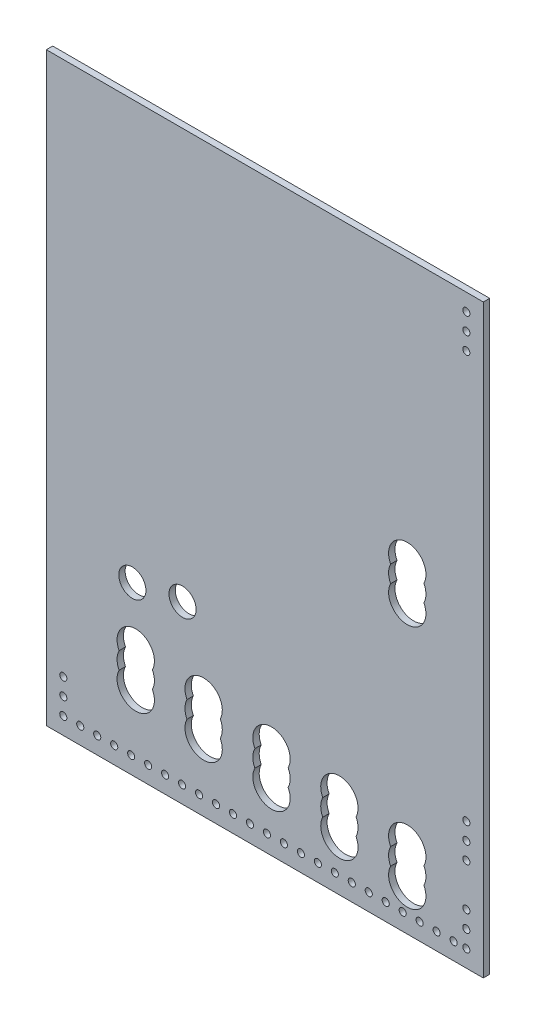
SolidWorks part; units mm, degrees
material "Polypropylene"
ref_plane "Front Plane" through (0, 0, 0) normal (0, 0, 1) x (1, 0, 0)
ref_plane "Top Plane" through (0, 0, 0) normal (0, 1, 0) x (1, 0, 0)
ref_plane "Right Plane" through (0, 0, 0) normal (1, 0, 0) x (0, 0, -1)
sketch "Sketch1" plane through (0, 0, 0) normal (0, 0, 1) x (1, 0, 0)
  line L0 (270.1144, -382.3444) -> (270.1144, -198.1944) construction
  line L1 (0, 0) -> (327.025, 0)
  line L2 (0, 0) -> (0, -438.15)
  line L3 (0, -438.15) -> (327.025, -438.15)
  line L4 (327.025, 0) -> (327.025, -438.15)
  line L5 (270.1144, -198.1944) -> (270.1144, -210.8944) construction
  line L6 (270.1144, -210.8944) -> (270.1144, -223.5944) construction
  arc A2 (257.671, -204.5444) -> (257.671, -217.2444) centre (270.1144, -210.8944) ccw
  arc A3 (257.671, -217.2444) -> (282.5578, -217.2444) centre (270.1144, -223.5944) ccw
  arc A4 (282.5578, -204.5444) -> (257.671, -204.5444) centre (270.1144, -198.1944) ccw
  circle A5 centre (101.9257, -306.8134) radius 10.16
  circle A6 centre (64.3744, -313.2564) radius 10.16
  arc A7 (282.5578, -217.2444) -> (282.5578, -204.5444) centre (270.1144, -210.8944) ccw
  dimension "D4" = 27.94
  dimension "D5" = 20.32
  dimension "D6" = 20.32
  dimension "D1" = 438.15
  dimension "D2" = 327.025
  dimension "D3" = 184.15
extrude "Boss-Extrude1" add sketch "Sketch1" along normal blind 4.7625
sketch "Sketch2" plane through (0, 0, 4.7625) normal (0, 0, 1) x (1, 0, 0)
  line L0 (66.9144, -355.9045) -> (66.9144, -368.6045) construction
  line L1 (66.9144, -368.6045) -> (66.9144, -381.3045) construction
  arc A0 (54.471, -362.2545) -> (54.471, -374.9545) centre (66.9144, -368.6045) ccw
  arc A2 (54.471, -374.9545) -> (79.3578, -374.9545) centre (66.9144, -381.3045) ccw
  arc A3 (79.3578, -374.9545) -> (79.3578, -362.2545) centre (66.9144, -368.6045) ccw
  arc A4 (79.3578, -362.2545) -> (54.471, -362.2545) centre (66.9144, -355.9045) ccw
  dimension "D2" = 27.94
extrude "Cut-Extrude1" cut sketch "Sketch2" against normal up to surface (4.7625 mm away) up to face at (74.5344, -313.2564, 0)
sketch "Sketch3" plane through (0, 0, 4.7625) normal (0, 0, 1) x (1, 0, 0)
  line L0 (66.9144, -355.9045) -> (327.025, -355.9045) construction
  line L1 (327.025, -438.15) -> (327.025, 0) construction
  line L2 (66.9144, -355.9045) -> (117.7144, -355.9045) construction
  line L3 (117.7144, -355.9045) -> (168.5144, -355.9045) construction
  line L4 (168.5144, -355.9045) -> (219.3144, -355.9045) construction
  line L5 (219.3144, -355.9045) -> (270.1144, -355.9045) construction
  line L6 (117.7144, -355.9045) -> (117.7144, -362.2545) construction
  line L7 (168.5144, -355.9045) -> (168.5144, -368.6045) construction
  line L8 (219.3144, -355.9045) -> (219.3144, -374.9545) construction
  line L9 (270.1144, -355.9045) -> (270.1144, -381.3045) construction
  line L10 (117.7144, -355.9045) -> (117.7144, -362.2545) construction
  line L11 (117.7144, -362.2545) -> (117.7144, -374.9545) construction
  line L12 (117.7144, -374.9545) -> (117.7144, -387.6545) construction
  line L13 (168.5144, -368.6045) -> (168.5144, -381.3045) construction
  line L14 (168.5144, -381.3045) -> (168.5144, -394.0045) construction
  line L15 (219.3144, -374.9545) -> (219.3144, -387.6545) construction
  line L16 (219.3144, -387.6545) -> (219.3144, -400.3545) construction
  line L17 (270.1144, -381.3045) -> (270.1144, -394.0045) construction
  line L18 (270.1144, -394.0045) -> (270.1144, -406.7045) construction
  arc A2 (231.7578, -381.3045) -> (206.871, -381.3045) centre (219.3144, -374.9545) ccw
  arc A3 (282.5578, -387.6545) -> (257.671, -387.6545) centre (270.1144, -381.3045) ccw
  arc A4 (105.271, -368.6045) -> (105.271, -381.3045) centre (117.7144, -374.9545) ccw
  arc A6 (105.271, -381.3045) -> (130.1578, -381.3045) centre (117.7144, -387.6545) ccw
  arc A8 (130.1578, -381.3045) -> (130.1578, -368.6045) centre (117.7144, -374.9545) ccw
  arc A9 (156.071, -374.9545) -> (156.071, -387.6545) centre (168.5144, -381.3045) ccw
  arc A10 (156.071, -387.6545) -> (180.9578, -387.6545) centre (168.5144, -394.0045) ccw
  arc A12 (180.9578, -387.6545) -> (180.9578, -374.9545) centre (168.5144, -381.3045) ccw
  arc A13 (206.871, -381.3045) -> (206.871, -394.0045) centre (219.3144, -387.6545) ccw
  arc A14 (206.871, -394.0045) -> (231.7578, -394.0045) centre (219.3144, -400.3545) ccw
  arc A15 (231.7578, -394.0045) -> (231.7578, -381.3045) centre (219.3144, -387.6545) ccw
  arc A16 (257.671, -387.6545) -> (257.671, -400.3545) centre (270.1144, -394.0045) ccw
  arc A17 (257.671, -400.3545) -> (282.5578, -400.3545) centre (270.1144, -406.7045) ccw
  arc A19 (282.5578, -400.3545) -> (282.5578, -387.6545) centre (270.1144, -394.0045) ccw
  arc A20 (130.1578, -368.6045) -> (105.271, -368.6045) centre (117.7144, -362.2545) ccw
  arc A21 (180.9578, -374.9545) -> (156.071, -374.9545) centre (168.5144, -368.6045) ccw
  dimension "D10" = 27.94
  dimension "D11" = 27.94
  dimension "D1" = 50.8
  dimension "D2" = 50.8
  dimension "D3" = 50.8
  dimension "D4" = 50.8
  dimension "D5" = 12.7
  dimension "D6" = 19.05
  dimension "D7" = 25.4
  dimension "D12" = 6.35
extrude "Cut-Extrude2" cut sketch "Sketch3" against normal up to surface (4.7625 mm away) contours A2 A13 A14 A15 | A3 A16 A17 A19 | A21 A9 A10 A12 | A20 A4 A6 A8 up to face at (66.9144, -368.6045, 0)
sketch "Sketch4" plane through (0, 0, 0) normal (0, 0, -1) x (-1, 0, 0)
  line L0 (-12.7, -438.15) -> (-12.7, -425.45) construction
  line L1 (0, -438.15) -> (-327.025, -438.15) construction
  line L2 (-12.7, -425.45) -> (0, -425.45) construction
  line L3 (0, 0) -> (0, -438.15) construction
  line L4 (-327.025, -425.45) -> (0, -425.45) construction
  line L5 (-327.025, 0) -> (0, 0) construction
  line L6 (-163.5125, 0) -> (-163.5125, -438.15) construction
  line L7 (-327.025, -438.15) -> (-327.025, 0) construction
  line L8 (-314.325, -438.15) -> (-314.325, -425.45) construction
  line L9 (-314.325, 0) -> (-314.325, -12.7) construction
  line L10 (-314.325, -400.05) -> (-314.325, -368.3) construction
  circle A0 centre (-12.7, -425.45) radius 2.667
  circle A1 centre (-12.7, -412.75) radius 2.667
  circle A2 centre (-12.7, -400.05) radius 2.667
  circle A38 centre (-314.325, -400.05) radius 2.667
  circle A39 centre (-314.325, -412.75) radius 2.667
  circle A40 centre (-314.325, -425.45) radius 2.667
  circle A44 centre (-12.7, -57.15) radius 2.667 [skipped]
  circle A45 centre (-12.7, -69.85) radius 2.667 [skipped]
  circle A46 centre (-12.7, -82.55) radius 2.667 [skipped]
  circle A47 centre (-12.7, -95.25) radius 2.667 [skipped]
  circle A48 centre (-12.7, -107.95) radius 2.667 [skipped]
  circle A49 centre (-12.7, -120.65) radius 2.667 [skipped]
  circle A50 centre (-12.7, -133.35) radius 2.667 [skipped]
  circle A51 centre (-12.7, -146.05) radius 2.667 [skipped]
  circle A52 centre (-12.7, -184.15) radius 2.667 [skipped]
  circle A53 centre (-12.7, -171.45) radius 2.667 [skipped]
  circle A54 centre (-12.7, -158.75) radius 2.667 [skipped]
  circle A55 centre (-12.7, -285.75) radius 2.667 [skipped]
  circle A56 centre (-12.7, -273.05) radius 2.667 [skipped]
  circle A57 centre (-12.7, -260.35) radius 2.667 [skipped]
  circle A58 centre (-12.7, -247.65) radius 2.667 [skipped]
  circle A59 centre (-12.7, -234.95) radius 2.667 [skipped]
  circle A60 centre (-12.7, -222.25) radius 2.667 [skipped]
  circle A61 centre (-12.7, -209.55) radius 2.667 [skipped]
  circle A62 centre (-12.7, -196.85) radius 2.667 [skipped]
  circle A63 centre (-12.7, -323.85) radius 2.667 [skipped]
  circle A64 centre (-12.7, -311.15) radius 2.667 [skipped]
  circle A65 centre (-12.7, -298.45) radius 2.667 [skipped]
  circle A66 centre (-25.4, -425.45) radius 2.667
  circle A67 centre (-38.1, -425.45) radius 2.667
  circle A68 centre (-50.8, -425.45) radius 2.667
  circle A69 centre (-63.5, -425.45) radius 2.667
  circle A70 centre (-76.2, -425.45) radius 2.667
  circle A71 centre (-88.9, -425.45) radius 2.667
  circle A72 centre (-101.6, -425.45) radius 2.667
  circle A73 centre (-114.3, -425.45) radius 2.667
  circle A74 centre (-127, -425.45) radius 2.667
  circle A75 centre (-139.7, -425.45) radius 2.667
  circle A76 centre (-152.4, -425.45) radius 2.667
  circle A77 centre (-165.1, -425.45) radius 2.667
  circle A78 centre (-177.8, -425.45) radius 2.667
  circle A79 centre (-190.5, -425.45) radius 2.667
  circle A80 centre (-203.2, -425.45) radius 2.667
  circle A81 centre (-215.9, -425.45) radius 2.667
  circle A82 centre (-228.6, -425.45) radius 2.667
  circle A83 centre (-241.3, -425.45) radius 2.667
  circle A84 centre (-254, -425.45) radius 2.667
  circle A85 centre (-266.7, -425.45) radius 2.667
  circle A86 centre (-279.4, -425.45) radius 2.667
  circle A87 centre (-292.1, -425.45) radius 2.667
  circle A88 centre (-304.8, -425.45) radius 2.667
  circle A89 centre (-12.7, -19.05) radius 2.667 [skipped]
  circle A90 centre (-12.7, -31.75) radius 2.667 [skipped]
  circle A91 centre (-12.7, -44.45) radius 2.667 [skipped]
  circle A92 centre (-314.325, -12.7) radius 2.667
  circle A93 centre (-314.325, -25.4) radius 2.667
  circle A94 centre (-314.325, -38.1) radius 2.667
  circle A95 centre (-314.325, -368.3) radius 2.667
  circle A96 centre (-314.325, -355.6) radius 2.667
  circle A97 centre (-314.325, -342.9) radius 2.667
  circle A98 centre (-12.7, -336.55) radius 2.667 [skipped]
  circle A99 centre (-12.7, -349.25) radius 2.667 [skipped]
  circle A100 centre (-12.7, -361.95) radius 2.667 [skipped]
  circle A101 centre (-12.7, -374.65) radius 2.667 [skipped]
  circle A102 centre (-12.7, -387.35) radius 2.667 [skipped]
  dimension "D3" = 5.334
  dimension "D8" = 5.334
  dimension "D9" = 5.334
  dimension "D1" = 12.7
  dimension "D2" = 12.7
  dimension "D4" = 24
  dimension "D6" = 12.7
  dimension "D11" = 31.75
  dimension "D5" = 33
  dimension "D7" = 3
  dimension "D10" = 3
extrude "Cut-Extrude3" cut sketch "Sketch4" against normal through all
